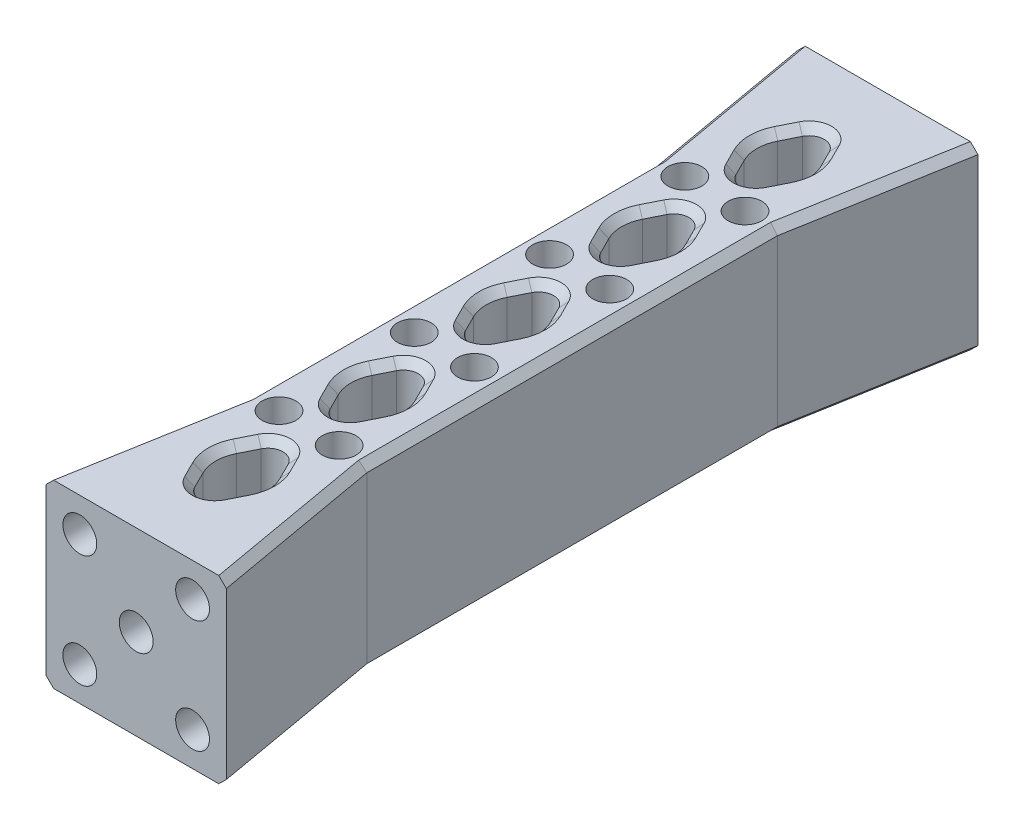
SolidWorks part; units mm, degrees
note: '?' marks a value the reader was unsure of.
material "ABS"
ref_plane "Front Plane" through (0, 0, 0) normal (0, 0, 1) x (1, 0, 0)
ref_plane "Top Plane" through (0, 0, 0) normal (0, 1, 0) x (1, 0, 0)
ref_plane "Right Plane" through (0, 0, 0) normal (1, 0, 0) x (0, 0, -1)
ref_axis "X" through (-88.99, 0, 0) along (1, 0, 0)?
ref_axis "Y" through (0, 55, 0) along (0, -1, 0)?
ref_axis "Z" through (0, 0, -88.99) along (0, 0, 1)?
sketch "Sketch1" plane through (0, 0, 0) normal (0, 1, 0) x (1, 0, 0)
  line L0 (0, 0) -> (8, 0)
  line L1 (8, 0) -> (8, -27.3149)
  line L2 (8, -27.3149) -> (12, -50)
  line L3 (12, -50) -> (0, -50)
  line L4 (0, -50) -> (0, 0)
  line L5 (4, 0) -> (0, -8)
  line L6 (0, -10) -> (4, -18)
  line L7 (4, -18) -> (0, -26)
  line L8 (0, -28) -> (4, -36)
  line L9 (4, -36) -> (0, -44)
  line L10 (4, 0) -> (4, -18) construction
  line L11 (4, -18) -> (4, -36) construction
  circle A0 centre (4, -9) radius 2.25
  circle A1 centre (4, -27) radius 2.25
  dimension "D8" = 4.5
  dimension "D1" = 50
  dimension "D2" = 80
  dimension "D3" = 8
  dimension "D4" = 12
  dimension "D5" = 8
  dimension "D6" = 2
  dimension "D7" = 2
extrude "Boss-Extrude1" add sketch "Sketch1" along normal mid plane 24 contours L8 L9 L4 L3 L2 L1 L0 L5 L6 L7
fillet "Fillet1" radius 5 2 edges at (4, 0, 18) (4, 0, 36)
mirror "Mirror1" about plane through (0, 0, 0) normal (1, 0, 0) of bodies 101
sketch "Sketch2" plane through (0, 0, 0) normal (0, 0, 1) x (1, 0, 0)
  line L1 (-7.5, 7.5) -> (7.5, 7.5) construction
  line L2 (-7.5, 7.5) -> (-7.5, -7.5) construction
  line L3 (-7.5, -7.5) -> (7.5, -7.5) construction
  line L4 (7.5, 7.5) -> (7.5, -7.5) construction
  line L5 (-7.5, 7.5) -> (7.5, -7.5) construction
  line L6 (-7.5, -7.5) -> (7.5, 7.5) construction
  circle A0 centre (-7.5, 7.5) radius 2.25
  circle A1 centre (0, 0) radius 2.25
  circle A2 centre (7.5, 7.5) radius 2.25
  circle A3 centre (7.5, -7.5) radius 2.25
  circle A4 centre (-7.5, -7.5) radius 2.25
  point P0 (0, 0)
  dimension "D2" = 4.5
  dimension "D1" = 15
extrude "Cut-Extrude1" cut sketch "Sketch2" against normal blind 5 from surface at 50 starting at face at (0, 0, 50)
fillet "Fillet3" radius 2 5 edges at (0, 0, 28) (0, 0, 10) (0, 0, 8) (0, 0, 26) (0, 0, 44)
mirror "Mirror2" about plane through (0, 0, 0) normal (0, 0, 1) of bodies 104 102
fillet "Fillet2" radius 5 2 edges at (-4, 0, 0) (4, 0, 0)
chamfer "Chamfer1" distance 1 angle 45 92 edges at (-3.4098, 12, 36) (-3.4098, -12, 36) (-2.3354, 12, 39.3292) (-2.3354, -12, 39.3292) (-2.3354, -12, 32.6708) (-2.3354, 12, 32.6708) (0, 12, 41.5279) (0, -12, 41.5279) (0, 12, 30.4721) (0, -12, 30.4721) (2.3354, -12, 39.3292) (2.3354, 12, 39.3292) (2.3354, 12, 32.6708) (2.3354, -12, 32.6708) (3.4098, 12, 36) (3.4098, -12, 36) (-3.4098, 12, 18) (-3.4098, -12, 18) (-2.3354, 12, 21.3292) (-2.3354, -12, 21.3292) (-2.3354, -12, 14.6708) (-2.3354, 12, 14.6708) (0, 12, 23.5279) (0, -12, 23.5279) (0, 12, 12.4721) (0, -12, 12.4721) (2.3354, -12, 21.3292) (2.3354, 12, 21.3292) (2.3354, 12, 14.6708) (2.3354, -12, 14.6708) (3.4098, 12, 18) (3.4098, -12, 18) (-3.4098, 12, 0) (-3.4098, -12, 0) (-2.3354, -12, 3.3292) (-2.3354, 12, 3.3292) (-2.3354, -12, -3.3292) (0, 12, 5.5279) (0, -12, 5.5279) (0, -12, -5.5279) (2.3354, 12, 3.3292) (2.3354, -12, 3.3292) (2.3354, -12, -3.3292) (3.4098, 12, 0) (3.4098, -12, 0) (-3.4098, -12, -18) (-2.3354, -12, -21.3292) (-2.3354, -12, -14.6708) (0, -12, -23.5279) (0, -12, -12.4721) (2.3354, -12, -21.3292) (2.3354, -12, -14.6708) (3.4098, -12, -18) (-3.4098, -12, -36) (-2.3354, -12, -39.3292) (-2.3354, -12, -32.6708) (0, -12, -41.5279) (0, -12, -30.4721) (2.3354, -12, -39.3292) (2.3354, -12, -32.6708) (3.4098, -12, -36) (3.4098, 12, -36) (2.3354, 12, -32.6708) (2.3354, 12, -39.3292) (0, 12, -30.4721) (0, 12, -41.5279) (-2.3354, 12, -32.6708) (-2.3354, 12, -39.3292) (-3.4098, 12, -36) (3.4098, 12, -18) (2.3354, 12, -14.6708) (2.3354, 12, -21.3292) (0, 12, -12.4721) (0, 12, -23.5279) (-2.3354, 12, -14.6708) (-2.3354, 12, -21.3292) (-3.4098, 12, -18) (2.3354, 12, -3.3292) (0, 12, -5.5279) (-2.3354, 12, -3.3292) (10, -12, -38.6574) (10, -12, 38.6574) (10, 12, 38.6574) (8, -12, 0) (8, 12, 0) (10, 12, -38.6574) (-10, -12, -38.6574) (-10, -12, 38.6574) (-10, 12, 38.6574) (-8, -12, 0) (-8, 12, 0) (-10, 12, -38.6574)
